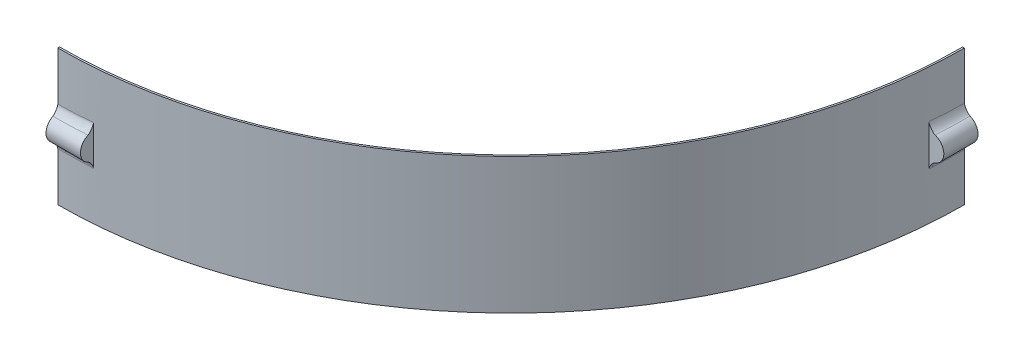
SolidWorks part; units mm, degrees
ref_plane "Front Plane" through (0, 0, 0) normal (0, 0, 1) x (1, 0, 0)
ref_plane "Top Plane" through (0, 0, 0) normal (0, 1, 0) x (1, 0, 0)
ref_plane "Right Plane" through (0, 0, 0) normal (1, 0, 0) x (0, 0, -1)
sketch "Sketch1" plane through (0, 0, 0) normal (0, 0, 1) x (1, 0, 0)
  line L0 (0, 3.3639) -> (0, -36.2756) construction
  line L1 (127.254, 19.05) -> (126.746, 19.05)
  line L2 (127.254, 19.05) -> (127.254, -19.05)
  line L3 (127.254, -19.05) -> (126.746, -19.05)
  line L4 (126.746, 19.05) -> (126.746, -19.05)
  line L5 (127.254, 19.05) -> (126.746, -19.05) construction
  line L6 (127.254, -19.05) -> (126.746, 19.05) construction
  point P0 (127, 0)
  dimension "D1" = 38.1
  dimension "D2" = 0.508
  dimension "D3" = 127
revolve "Revolve1" add sketch "Sketch1" angle 90 about L0
sketch "Sketch4" plane through (0, 0, 0) normal (-1, 0, 0) x (0, 0, 1)
  line L0 (126.746, 19.05) -> (126.746, -19.05) construction
  circle A0 centre (127, 0) radius 3.556
  point P2 (126.746, 0)
  dimension "D2" = 7.112
  dimension "D1" = 0.254
extrude "Boss-Extrude1" add sketch "Sketch4" against normal blind 9.652
sketch "Sketch6" plane through (9.652, 0, 0) normal (1, 0, 0) x (0, 0, -1)
  circle A0 centre (-127, 0) radius 3.175
  circle A2 centre (-127, 0) radius 3.556 construction
fillet "Fillet6" radius 2.54 2 edges at (7.112, 3.5556, 127.0551) (2.5454, -3.5486, 127.2285)
fillet "Fillet8" radius 2.54 2 edges at (7.112, -3.5269, 126.5463) (2.5454, 3.545, 126.7204)
sketch "Sketch7" plane through (0, 0, 0) normal (0, 0, -1) x (-1, 0, 0)
  line L0 (-127.254, -19.05) -> (-127.254, 19.05) construction
  circle A0 centre (-127.508, 0) radius 3.556
  point P2 (-127.254, 0)
  dimension "D1" = 7.112
  dimension "D2" = 0.254
extrude "Boss-Extrude2" add sketch "Sketch7" against normal blind 9.6012
sketch "Sketch8" plane through (0, 0, 9.6012) normal (0, 0, 1) x (1, 0, 0)
  circle A0 centre (127.508, 0) radius 3.175
  circle A1 centre (127.508, 0) radius 3.556 construction
  dimension "D1" = 6.35
fillet "Fillet11" radius 2.54 4 edges at (126.5463, 3.4235, 7.112) (126.7214, -3.4679, 2.4946) (127.0551, -3.527, 7.112) (127.2296, 3.5451, 2.4944)
sketch "Sketch9" plane through (0, 0, 0) normal (-1, 0, 0) x (0, 0, 1)
  circle A0 centre (127, 0) radius 3.175
  dimension "D1" = 6.35
extrude "Cut-Extrude1" cut sketch "Sketch9" against normal blind 9.525
sketch "Sketch10" plane through (0, 0, 0) normal (0, 0, -1) x (-1, 0, 0)
  circle A0 centre (-127.508, 0) radius 3.175
extrude "Cut-Extrude2" cut sketch "Sketch10" against normal blind 9.525
